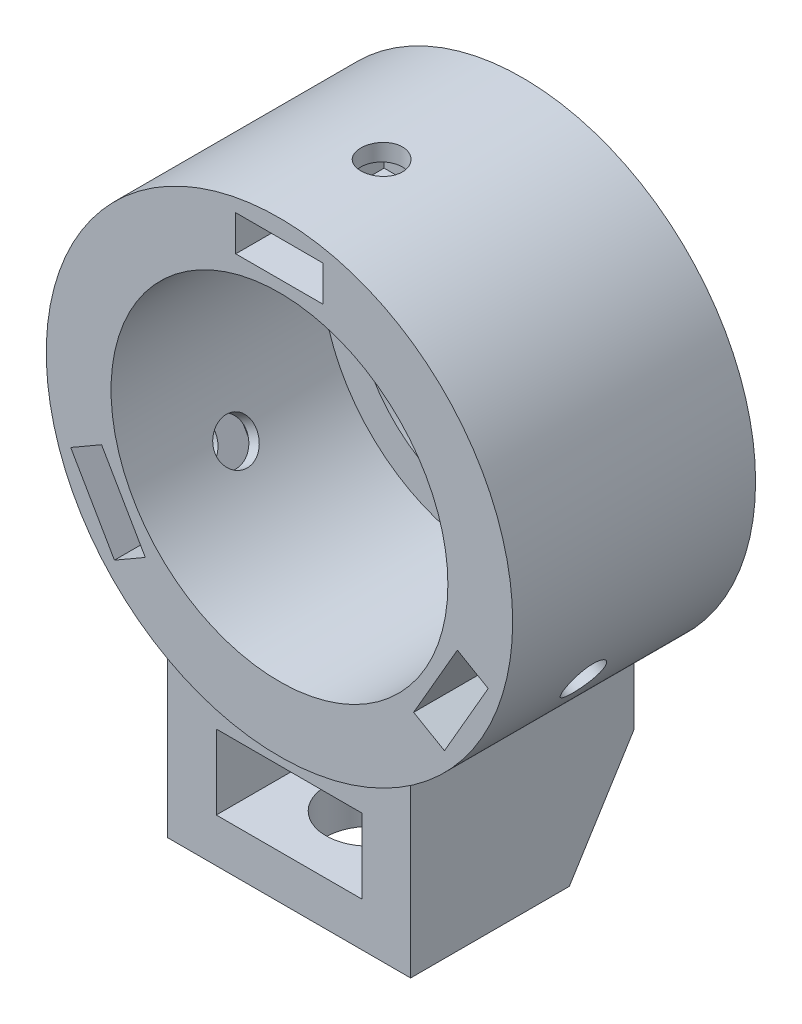
SolidWorks part; units mm, degrees
ref_plane "Front Plane" through (0, 0, 0) normal (0, 0, 1) x (1, 0, 0)
ref_plane "Top Plane" through (0, 0, 0) normal (0, 1, 0) x (1, 0, 0)
ref_plane "Right Plane" through (0, 0, 0) normal (1, 0, 0) x (0, 0, -1)
sketch "Sketch1" plane through (0, 0, 0) normal (0, 0, 1) x (1, 0, 0)
  circle A0 centre (0, 0) radius 18.288
  dimension "D1" = 36.576
extrude "Boss-Extrude1" add sketch "Sketch1" along normal blind 19.05
sketch "Sketch3" plane through (0, 0, 19.05) normal (0, 0, 1) x (1, 0, 0)
  circle A0 centre (0, 0) radius 13.208
  dimension "D2" = 26.416
extrude "Cut-Extrude1" cut sketch "Sketch3" against normal offset from surface (16.51 mm away) 2.54 up to face at (18.288, 0, 0)
sketch "Sketch6" plane through (0, 0, 2.54) normal (0, 0, 1) x (1, 0, 0)
  circle A0 centre (0, 0) radius 10.668
  circle A1 centre (0, 0) radius 13.208 construction
  dimension "D1" = 2.54
extrude "Cut-Extrude2" cut sketch "Sketch6" against normal up to next
ref_plane "Plane1" through (0, 10.16, 0) normal (0, 1, 0) x (1, 0, 0)
sketch "Sketch10" plane through (0, 0, 19.05) normal (0, 0, 1) x (1, 0, 0)
  line L1 (-3.429, 14.1294) -> (3.429, 14.1294)
  line L2 (-3.429, 14.1294) -> (-3.429, 16.9234)
  line L3 (-3.429, 16.9234) -> (3.429, 16.9234)
  line L4 (3.429, 14.1294) -> (3.429, 16.9234)
  line L5 (-3.429, 14.1294) -> (3.429, 16.9234) construction
  line L6 (-3.429, 16.9234) -> (3.429, 14.1294) construction
  point P0 (0, 15.5264)
  dimension "D2" = 6.858
  dimension "D1" = 2.794
extrude "Cut-Extrude3" cut sketch "Sketch10" against normal blind 11.6383
pattern_circular "CirPattern1" count 3 over 360 about axis through (0, 0, 19.05) along (0, 0, -1) of "Cut-Extrude3"
hole_wizard "#4 Clearance Hole1" positions "Sketch12" profile "Sketch13" hole size "#4" standard "ANSI Inch"
sketch "Sketch12" plane through (0, 10.16, 0) normal (0, 1, 0) x (1, 0, 0)
  line L0 (0, -19.05) -> (0, 0) construction
  point P0 (0, -11.0392)
sketch "Sketch13" plane through (0, 10.16, 11.0392) normal (1, 0, 0) x (0, 0, -1)
  line L0 (0, 0) -> (0, 13.6806)
  line L1 (0, 13.6806) -> (1.6319, 12.7)
  line L2 (1.6319, 12.7) -> (1.6319, 0)
  line L5 (1.6319, 0) -> (0, 0)
  line L10 (0, 13.6806) -> (-1.632, 12.7) construction
  line L11 (0, -6.35) -> (0, 107.95) construction
  dimension "Hole Dia." = 3.2639
  dimension "Hole Depth" = 12.7
  dimension "Drill Angle" = 118
pattern_circular "CirPattern2" count 3 over 360 about axis through (0, 0, 19.05) along (0, 0, -1) of "#4 Clearance Hole1"
ref_plane "Plane2" through (0, -13.716, 0) normal (0, 1, 0) x (1, 0, 0)
sketch "Sketch15" plane through (0, -13.716, 0) normal (0, 1, 0) x (1, 0, 0)
  line L0 (0, -19.05) -> (0, 0) construction
  line L1 (-9.525, -0.762) -> (9.525, -0.762)
  line L2 (-9.525, -0.762) -> (-9.525, -18.288)
  line L3 (-9.525, -18.288) -> (9.525, -18.288)
  line L4 (9.525, -0.762) -> (9.525, -18.288)
  line L5 (-9.525, -0.762) -> (9.525, -18.288) construction
  line L6 (-9.525, -18.288) -> (9.525, -0.762) construction
  line L7 (-13.208, -19.05) -> (13.208, -19.05) construction
  line L8 (18.288, 0) -> (-18.288, 0) construction
  point P0 (0, -9.525)
  dimension "D1" = 19.05
  dimension "D2" = 0.762
  dimension "D3" = 0.762
extrude "Boss-Extrude3" add sketch "Sketch15" against normal blind 15.24
sketch "Sketch16" plane through (0, 0, 18.288) normal (0, 0, 1) x (1, 0, 0)
  line L0 (-9.525, -28.956) -> (-9.525, -15.6117) construction
  line L1 (-5.715, -25.5076) -> (5.715, -25.5076)
  line L2 (-5.715, -25.5076) -> (-5.715, -19.6656)
  line L3 (-5.715, -19.6656) -> (5.715, -19.6656)
  line L4 (5.715, -25.5076) -> (5.715, -19.6656)
  line L5 (-5.715, -25.5076) -> (5.715, -19.6656) construction
  line L6 (-5.715, -19.6656) -> (5.715, -25.5076) construction
  point P0 (0, -22.5866)
  dimension "D1" = 5.842
  dimension "D2" = 11.43
  dimension "D3" = 3.81
extrude "Cut-Extrude4" cut sketch "Sketch16" against normal through all
chamfer "Chamfer1" distance 5.08 angle 58 1 edges at (0, -28.956, 0.762) first distance on face at (0, -28.956, 9.525)
hole_wizard "1/4 Clearance Hole1" positions "Sketch18" profile "Sketch17" hole size "1/4" standard "ANSI Inch" end condition up to next
sketch "Sketch18" plane through (0, -28.956, 0) normal (0, -1, 0) x (-1, 0, 0)
  line L0 (0, -18.288) -> (0, -0.762) construction
  point P0 (0, -12.0214)
sketch "Sketch17" plane through (0, -28.956, 12.0214) normal (1, 0, 0) x (0, 0, -1)
  line L0 (0, 0) -> (0, 3.4484)
  line L1 (0, 3.4484) -> (3.3782, 3.4484)
  line L2 (3.3782, 3.4484) -> (3.3782, 0)
  line L5 (3.3782, 0) -> (0, 0)
  line L11 (0, -6.35) -> (0, 107.95) construction
  dimension "Thru Hole Dia." = 6.7564
  dimension "Thru Hole Depth" = 3.4484
